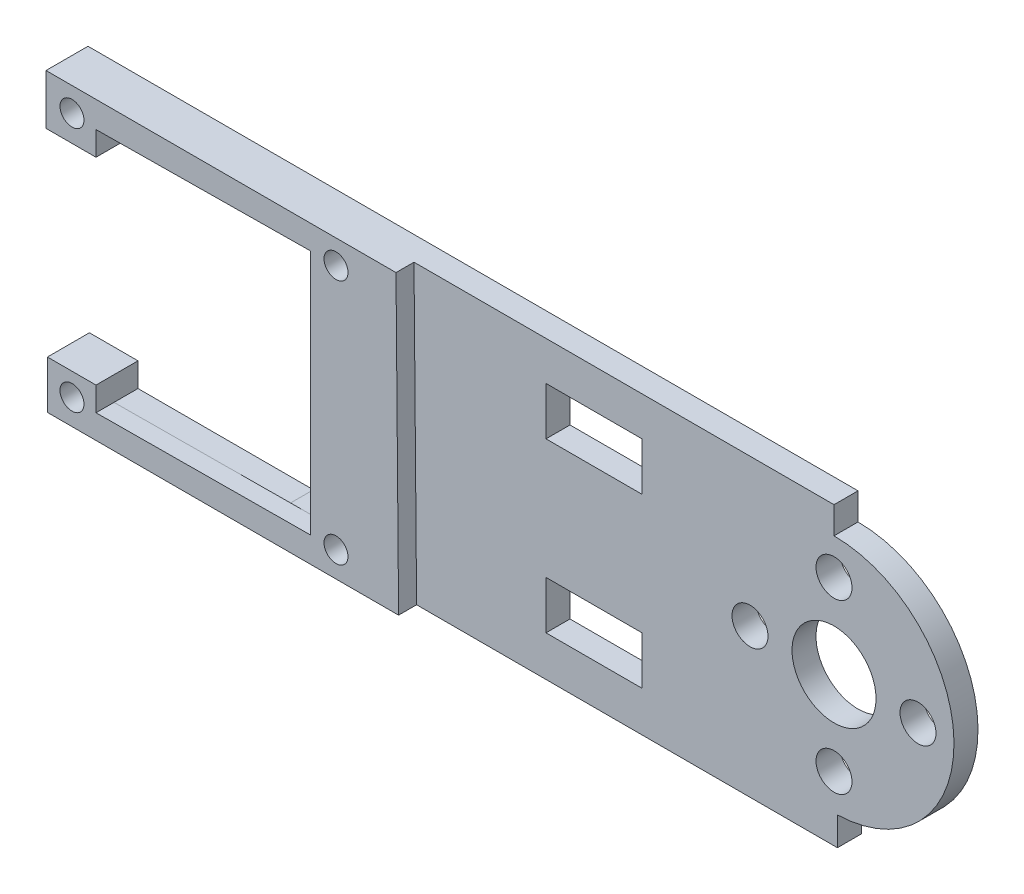
SolidWorks part; units mm, degrees
ref_plane "Front Plane" through (0, 0, 0) normal (0, 0, 1) x (1, 0, 0)
ref_plane "Top Plane" through (0, 0, 0) normal (0, 1, 0) x (1, 0, 0)
ref_plane "Right Plane" through (0, 0, 0) normal (1, 0, 0) x (0, 0, -1)
sketch "Sketch1" plane through (0, 0, 0) normal (0, 0, 1) x (1, 0, 0)
  line L1 (-5.1665, 12.25) -> (5, 12.25)
  line L3 (-5.0482, -12.3681) -> (5.2163, -12.3681)
  line L5 (-5.1665, 12.25) -> (5.2163, -12.3681) construction
  line L6 (-5.0482, -12.3681) -> (5, 12.25) construction
  line L12 (5, 12.25) -> (40, 12.25)
  line L13 (40, 12.25) -> (40, 10)
  line L14 (40.2847, -12.3681) -> (5.2163, -12.3681)
  line L15 (-5.3849, 10.25) -> (-2.1349, 10.25)
  line L16 (40.2847, -9.9959) -> (40.2847, -12.3681)
  line L17 (16, 9) -> (24, 9)
  line L18 (16, 9) -> (16, 5)
  line L19 (16, 5) -> (24, 5)
  line L20 (24, 9) -> (24, 5)
  line L21 (16, 9) -> (24, 5) construction
  line L22 (16, 5) -> (24, 9) construction
  line L23 (16, -5) -> (24, -5)
  line L24 (16, -5) -> (16, -9)
  line L25 (16, -9) -> (24, -9)
  line L26 (24, -5) -> (24, -9)
  line L27 (16, -5) -> (24, -9) construction
  line L28 (16, -9) -> (24, -5) construction
  line L29 (-2.1349, 10.25) -> (-2.1349, -10.25)
  line L30 (-2.1349, -10.25) -> (-5.3849, -10.3681)
  line L31 (-5.1665, 12.25) -> (-24.1665, 12.25)
  line L44 (-24.1665, 12.25) -> (-24.1665, 8.0708)
  line L45 (-24.1665, 8.0708) -> (-20, 8.0708)
  line L46 (-20, 8.0708) -> (-20, 10.0708)
  line L47 (-20, 10.0708) -> (-5.3849, 10.25)
  line L48 (-5.0482, -12.3681) -> (-24.0482, -12.3681)
  line L49 (-24.0482, -12.3681) -> (-24.0482, -8.3681)
  line L50 (-24.0482, -8.3681) -> (-20, -8.3681)
  line L51 (-20, -8.3681) -> (-20, -10.3681)
  line L52 (-20, -10.3681) -> (-5.3849, -10.3681)
  circle A0 centre (0, 10.25) radius 1
  circle A1 centre (0, -10.25) radius 1
  arc A2 (40.2847, -9.9959) -> (40, 10) centre (40, 0) ccw
  circle A3 centre (40, 7) radius 1.5
  circle A4 centre (47, 0) radius 1.5
  circle A5 centre (40, -7) radius 1.5
  circle A6 centre (33, 0) radius 1.5
  circle A7 centre (40, 0) radius 3.5
  circle A10 centre (-22, 10.25) radius 1
  circle A11 centre (-22, -10.25) radius 1
  point P4 (0, 0)
  point P22 (20, 7)
  point P35 (20, -7)
  point P52 (0, 0)
  point P54 (0, 0)
  point P57 (0, 0)
  dimension "D3" = 2
  dimension "D4" = 2
  dimension "D11" = 20
  dimension "D12" = 3
  dimension "D15" = 7
  dimension "D6" = 2
  dimension "D7" = 2
  dimension "D1" = 20.5
  dimension "D2" = 10.25
  dimension "D5" = 2
  dimension "D8" = 22
  dimension "D9" = 2
  dimension "D10" = 35
  dimension "D13" = 7
  dimension "D16" = 2
  dimension "D17" = 3.25
  dimension "D18" = 3.25
  dimension "D19" = 20
  dimension "D20" = 4
  dimension "D21" = 4
  dimension "D22" = 8
  dimension "D23" = 8
  dimension "D24" = 40
  dimension "D25" = 3.25
  dimension "D26" = 2
  dimension "D27" = 2
  dimension "D28" = 19
  dimension "D29" = 19
  dimension "D14" = 4
extrude "Boss-Extrude1" add sketch "Sketch1" along normal blind 2
sketch "Sketch5" plane through (0, 0, 2) normal (0, 0, 1) x (1, 0, 0)
  line L12 (-24.1665, 12.25) -> (-24.1665, 8.0708)
  line L13 (-24.1665, 8.0708) -> (-20, 8.0708)
  line L14 (-20, 8.0708) -> (-20, 10.0708)
  line L15 (-20, 10.0708) -> (-2.1349, 10.25)
  line L16 (-2.1349, 10.25) -> (-2.1349, -10.25)
  line L17 (-2.1349, -10.25) -> (-20, -10.3681)
  line L18 (-20, -10.3681) -> (-20, -8.3681)
  line L19 (-20, -8.3681) -> (-24.0482, -8.3681)
  line L20 (-24.0482, -8.3681) -> (-24.0482, -12.3681)
  line L21 (-24.0482, -12.3681) -> (5.2163, -12.3681)
  line L22 (5.2163, -12.3681) -> (5, 12.25)
  line L23 (5, 12.25) -> (-24.1665, 12.25)
  circle A0 centre (-22, 10.25) radius 1
  circle A1 centre (-22, -10.25) radius 1
  circle A2 centre (0, -10.25) radius 1
  circle A3 centre (0, 10.25) radius 1
extrude "Boss-Extrude2" add sketch "Sketch5" along normal blind 1.5
